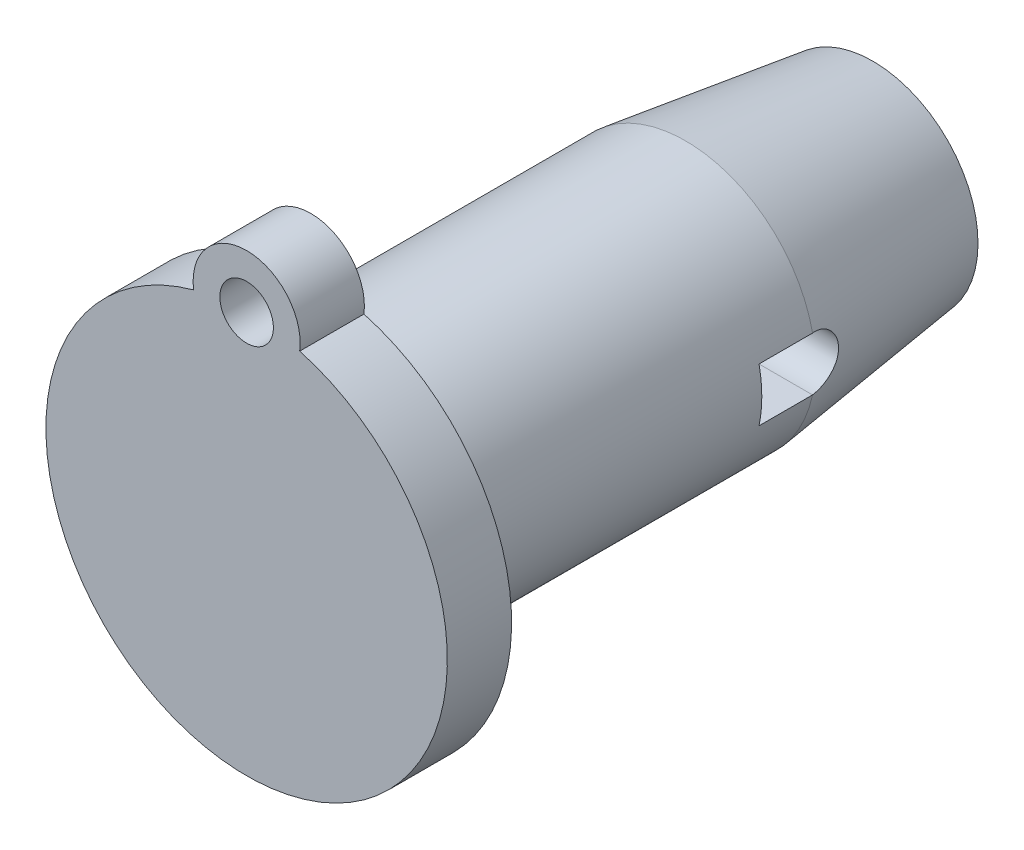
SolidWorks part; units mm, degrees
ref_plane "前视基准面" through (0, 0, 0) normal (0, 0, 1) x (1, 0, 0)
ref_plane "上视基准面" through (0, 0, 0) normal (0, 1, 0) x (1, 0, 0)
ref_plane "右视基准面" through (0, 0, 0) normal (1, 0, 0) x (0, 0, -1)
sketch "草图1" plane through (0, 0, 0) normal (0, 0, 1) x (1, 0, 0)
  circle A0 centre (0, 0) radius 37.5
  dimension "D1" = 75
extrude "拉伸1" add sketch "草图1" along normal blind 12
sketch "草图2" plane through (0, 0, 0) normal (0, 0, -1) x (-1, 0, 0)
  circle A0 centre (0, 0) radius 24.25
  dimension "D1" = 48.5
extrude "拉伸2" add sketch "草图2" along normal blind 105
chamfer "倒角1" distance 35 angle 7.5 1 edges at (-24.25, 0, -105) first distance on face at (-24.25, 0, -105)
ref_plane "基准面1" through (100, 0, 0) normal (1, 0, 0) x (0, 0, -1)
sketch "草图3" plane through (100, 0, 0) normal (1, 0, 0) x (0, 0, -1)
  line L1 (60, 5) -> (70, 5)
  line L2 (60, 5) -> (60, -5)
  line L3 (60, -5) -> (70, -5)
  arc A0 (70, 5) -> (70, -5) centre (70, 0) cw
  dimension "D1" = 10
  dimension "D2" = 10
  dimension "D3" = 60
  dimension "D4" = 5
extrude "拉伸3" cut sketch "草图3" against normal through all
sketch "草图6" plane through (0, 0, 0) normal (0, 0, -1) x (-1, 0, 0)
  circle A0 centre (0, 37.5) radius 10
  circle A2 centre (0, 0) radius 37.5 construction
  dimension "D1" = 20
extrude "拉伸4" add sketch "草图6" against normal blind 12
sketch "草图7" plane through (0, 0, 0) normal (0, 0, -1) x (-1, 0, 0)
  circle A0 centre (0, 37.5) radius 5
  arc A1 (-9.9107, 36.1667) -> (9.9107, 36.1667) centre (0, 0) ccw construction
  dimension "D1" = 10
extrude "拉伸5" cut sketch "草图7" against normal through all
